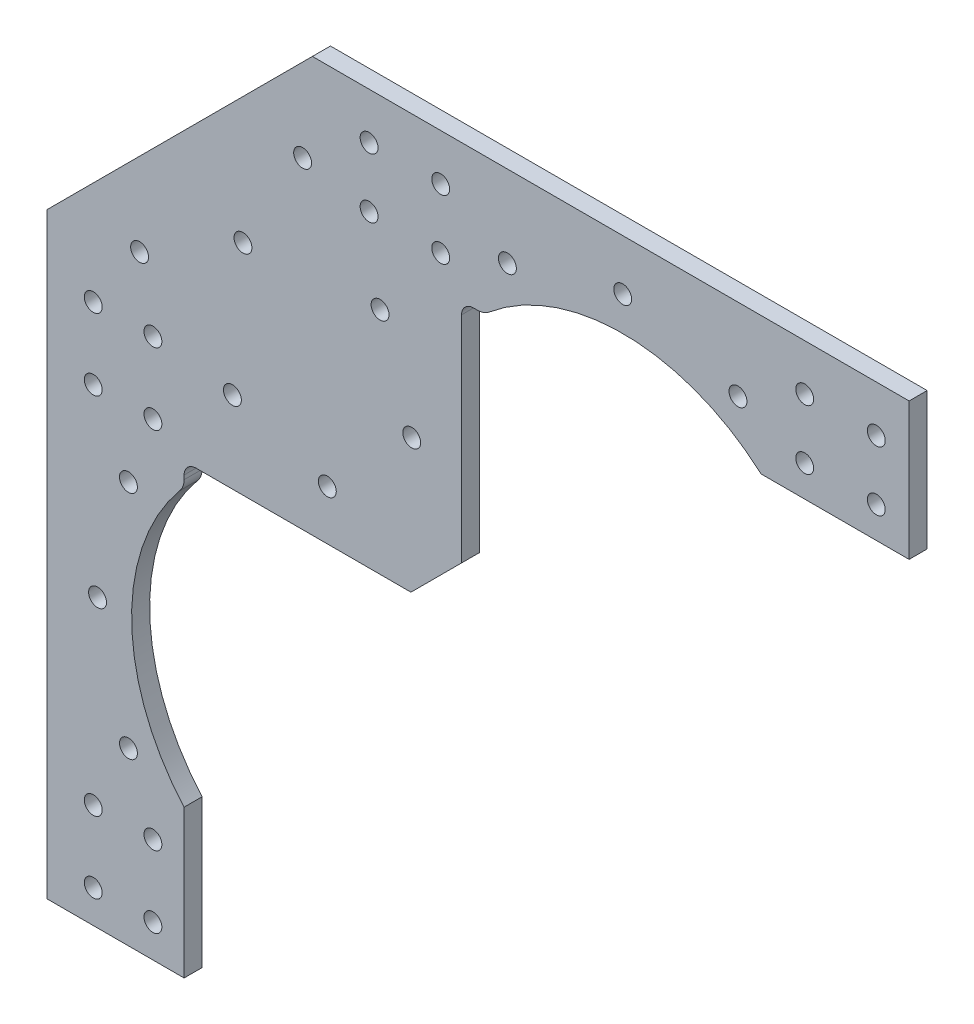
SolidWorks part; units mm, degrees
ref_plane "Front Plane" through (0, 0, 0) normal (0, 0, 1) x (1, 0, 0)
ref_plane "Top Plane" through (0, 0, 0) normal (0, 1, 0) x (1, 0, 0)
ref_plane "Right Plane" through (0, 0, 0) normal (1, 0, 0) x (0, 0, -1)
sketch "Sketch1" plane through (0, 0, 0) normal (0, 0, 1) x (1, 0, 0)
  line L0 (0, 0) -> (0, 73.5) construction
  line L1 (-96.5, -48) -> (-73.5, -48)
  line L2 (-96.5, -48) -> (-96.5, 52)
  line L4 (-73.5, -48) -> (-73.5, 27) construction
  line L5 (-52, 96.5) -> (48, 96.5)
  line L7 (-27, 73.5) -> (48, 73.5) construction
  line L8 (48, 96.5) -> (48, 73.5)
  line L9 (0, 0) -> (-73.5, 0) construction
  line L10 (-27, 73.5) -> (-73.5, 27) construction
  line L11 (-73.5, 73.5) -> (-27, 73.5) construction
  line L12 (-73.5, 27) -> (-73.5, 73.5) construction
  line L13 (-52, 96.5) -> (-96.5, 52)
  line L14 (-96.5, 96.5) -> (-52, 96.5) construction
  line L15 (-96.5, 52) -> (-96.5, 96.5) construction
  line L16 (-24.3179, 73.5) -> (-25, 73.5)
  line L17 (23.2069, 73.5) -> (48, 73.5)
  line L18 (-73.5, 25) -> (-73.5, 24.3179)
  line L19 (-73.5, -48) -> (-73.5, -23.2069)
  line L20 (-73.5, 23.2069) -> (-73.5, -23.2069) construction
  line L21 (-23.2069, 73.5) -> (23.2069, 73.5) construction
  line L22 (-71.5, 27) -> (-35.4853, 27)
  line L23 (-27, 35.4853) -> (-27, 71.5)
  line L24 (-35.4853, 27) -> (-27, 35.4853)
  line L25 (-25, 73.5) -> (-27, 73.5) construction
  line L26 (-27, 71.5) -> (-27, 73.5) construction
  line L27 (-73.5, 27) -> (-73.5, 25) construction
  line L28 (-73.5, 27) -> (-71.5, 27) construction
  line L29 (-23.2069, 73.5) -> (-24.3179, 73.5) construction
  line L30 (-73.5, 24.3179) -> (-73.5, 23.2069) construction
  arc A0 (23.2069, 73.5) -> (-22.3981, 74.1947) centre (0, 47.3) ccw
  arc A1 (-74.1947, 22.3981) -> (-73.5, -23.2069) centre (-47.3, 0) ccw
  arc A2 (-25, 73.5) -> (-27, 71.5) centre (-25, 71.5) ccw
  arc A3 (-71.5, 27) -> (-73.5, 25) centre (-71.5, 25) ccw
  arc A4 (-24.3179, 73.5) -> (-22.3981, 74.1947) centre (-24.3179, 76.5) ccw
  arc A5 (-22.3981, 74.1947) -> (-23.2069, 73.5) centre (0, 47.3) ccw construction
  arc A6 (-73.5, 24.3179) -> (-74.1947, 22.3981) centre (-76.5, 24.3179) cw
  arc A7 (-73.5, 23.2069) -> (-74.1947, 22.3981) centre (-47.3, 0) ccw construction
  dimension "D6" = 35
  dimension "D10" = 2
  dimension "D11" = 3
  dimension "D1" = 135
  dimension "D2" = 23
  dimension "D3" = 73.5
  dimension "D4" = 48
  dimension "D8" = 27
  dimension "D9" = 12
  dimension "D5" = 100
  dimension "D7" = 26.2
extrude "Boss-Extrude1" add sketch "Sketch1" along normal blind 3.0226
ref_axis "Axis1" through (0, 0, -0.1511) along (0, 0, 1)
sketch "Sketch3" plane through (0, 0, 3.0226) normal (0, 0, 1) x (1, 0, 0)
  line L1 (30.5, 88.7259) -> (30.5, 78.7259) construction
  line L2 (30.5, 88.7259) -> (42.5, 88.7259) construction
  line L3 (42.5, 88.7259) -> (42.5, 78.7259) construction
  line L4 (30.5, 78.7259) -> (42.5, 78.7259) construction
  line L16 (-30.5, 78.7259) -> (0, 78.7259) construction
  line L17 (0, 78.7259) -> (0, 0) construction
  line L18 (0, 78.7259) -> (30.5, 78.7259) construction
  line L19 (-78.7259, 0) -> (0, 0) construction
  line L20 (-78.7259, -30.5) -> (-78.7259, 0) construction
  line L21 (-78.7259, 0) -> (-78.7259, 30.5) construction
  line L30 (-42.5, 88.7259) -> (-42.5, 78.7259) construction
  line L31 (-42.5, 88.7259) -> (-30.5, 88.7259) construction
  line L32 (-30.5, 88.7259) -> (-30.5, 78.7259) construction
  line L33 (-42.5, 78.7259) -> (-30.5, 78.7259) construction
  line L34 (-88.7259, 42.5) -> (-88.7259, 30.5) construction
  line L35 (-88.7259, 42.5) -> (-78.7259, 42.5) construction
  line L36 (-78.7259, 42.5) -> (-78.7259, 30.5) construction
  line L37 (-88.7259, 30.5) -> (-78.7259, 30.5) construction
  line L38 (-88.7259, -30.5) -> (-88.7259, -42.5) construction
  line L39 (-88.7259, -30.5) -> (-78.7259, -30.5) construction
  line L40 (-78.7259, -30.5) -> (-78.7259, -42.5) construction
  line L41 (-88.7259, -42.5) -> (-78.7259, -42.5) construction
  circle A0 centre (30.5, 78.7259) radius 1.5
  circle A1 centre (30.5, 88.7259) radius 1.5
  circle A2 centre (42.5, 88.7259) radius 1.5
  circle A3 centre (42.5, 78.7259) radius 1.5
  circle A24 centre (-42.5, 78.7259) radius 1.5
  circle A25 centre (-42.5, 88.7259) radius 1.5
  circle A26 centre (-30.5, 88.7259) radius 1.5
  circle A27 centre (-30.5, 78.7259) radius 1.5
  circle A28 centre (-88.7259, 30.5) radius 1.5
  circle A29 centre (-88.7259, 42.5) radius 1.5
  circle A30 centre (-78.7259, 42.5) radius 1.5
  circle A31 centre (-78.7259, 30.5) radius 1.5
  circle A32 centre (-88.7259, -42.5) radius 1.5
  circle A33 centre (-88.7259, -30.5) radius 1.5
  circle A34 centre (-78.7259, -30.5) radius 1.5
  circle A35 centre (-78.7259, -42.5) radius 1.5
  dimension "D1" = 3
  dimension "D8" = 30.5
  dimension "D2" = 12
  dimension "D6" = 10
  dimension "D3" = 78.7259
extrude "Cut-Extrude1" cut sketch "Sketch3" against normal blind 10
sketch "Sketch4" plane through (0, 0, 3.0226) normal (0, 0, 1) x (1, 0, 0)
  line L0 (0, 0) -> (0, 88) construction
  line L1 (0, 0) -> (-63.6396, 63.6396) construction
  line L2 (0, 0) -> (-88, 0) construction
  line L3 (-82.8236, 19.3185) -> (-88, 0) construction
  line L4 (-88, 0) -> (-82.8236, -19.3185) construction
  line L5 (-80.9601, 53.6396) -> (-63.6396, 63.6396) construction
  line L6 (-63.6396, 63.6396) -> (-83.2677, 83.2677) construction
  line L7 (-19.3185, 82.8236) -> (0, 88) construction
  line L8 (-65.4074, 40.6586) -> (-40.6586, 65.4074) construction
  line L9 (-35.3553, 49.4975) -> (-49.4975, 35.3553) construction
  line L10 (-73.5, -48) -> (-73.5, -23.2069) construction
  line L11 (-35.4853, 27) -> (-27, 35.4853) construction
  circle A0 centre (-88, 0) radius 1.5
  circle A1 centre (-63.6396, 63.6396) radius 1.5
  circle A2 centre (0, 88) radius 1.5
  circle A3 centre (-80.9601, 53.6396) radius 1.5
  circle A4 centre (-53.6396, 80.9601) radius 1.5
  circle A5 centre (19.3185, 82.8236) radius 1.5
  circle A6 centre (-19.3185, 82.8236) radius 1.5
  circle A7 centre (-82.8236, 19.3185) radius 1.5
  circle A8 centre (-82.8236, -19.3185) radius 1.5
  circle A9 centre (-40.6586, 65.4074) radius 1.5
  circle A10 centre (-65.4074, 40.6586) radius 1.5
  circle A11 centre (-49.4975, 35.3553) radius 1.5
  circle A12 centre (-35.3553, 49.4975) radius 1.5
  dimension "D2" = 3
  dimension "D1" = 45
  dimension "D3" = 14.5
  dimension "D4" = 75
  dimension "D5" = 20
  dimension "D6" = 45.8162
  dimension "D7" = 75
  dimension "D8" = 75
  dimension "D9" = 35
  dimension "D10" = 20
  dimension "D11" = 15
  dimension "D12" = 15
extrude "Cut-Extrude2" cut sketch "Sketch4" against normal through all
ref_plane "Plane1" through (0, 0, 0) normal (-0.7071, -0.7071, 0) x (-0.7071, 0.7071, 0)
sketch "Sketch5" plane through (0, 0, 3.0226) normal (0, 0, 1) x (1, 0, 0)
  circle A0 centre (-76.6198, 82.5365) radius 9.6037
  point P2 (-76.6198, 82.5365)
equation "\"EyeDiameter\" = 35"
equation "\"BasePlaneDistance\" = \"EyeDiameter\"/2+19.84"
equation "\"EyeClearance\" = 2"
equation "\"L2Thickness\" = 8"
equation "\"L2_ID\" = 20"
equation "\"Offset\"= - 2"
equation "\"D3@Sketch1\"=\"BasePlaneDistance\" + 38.16 +\"Offset\""
equation "\"D3@Sketch3\"=\"BasePlaneDistance\" - 37.34+78.72592343"
equation "\"D7@Sketch1\"=24.20 - \"Offset\""
equation "\"D2@Sketch1\"=25.00 + \"Offset\""
